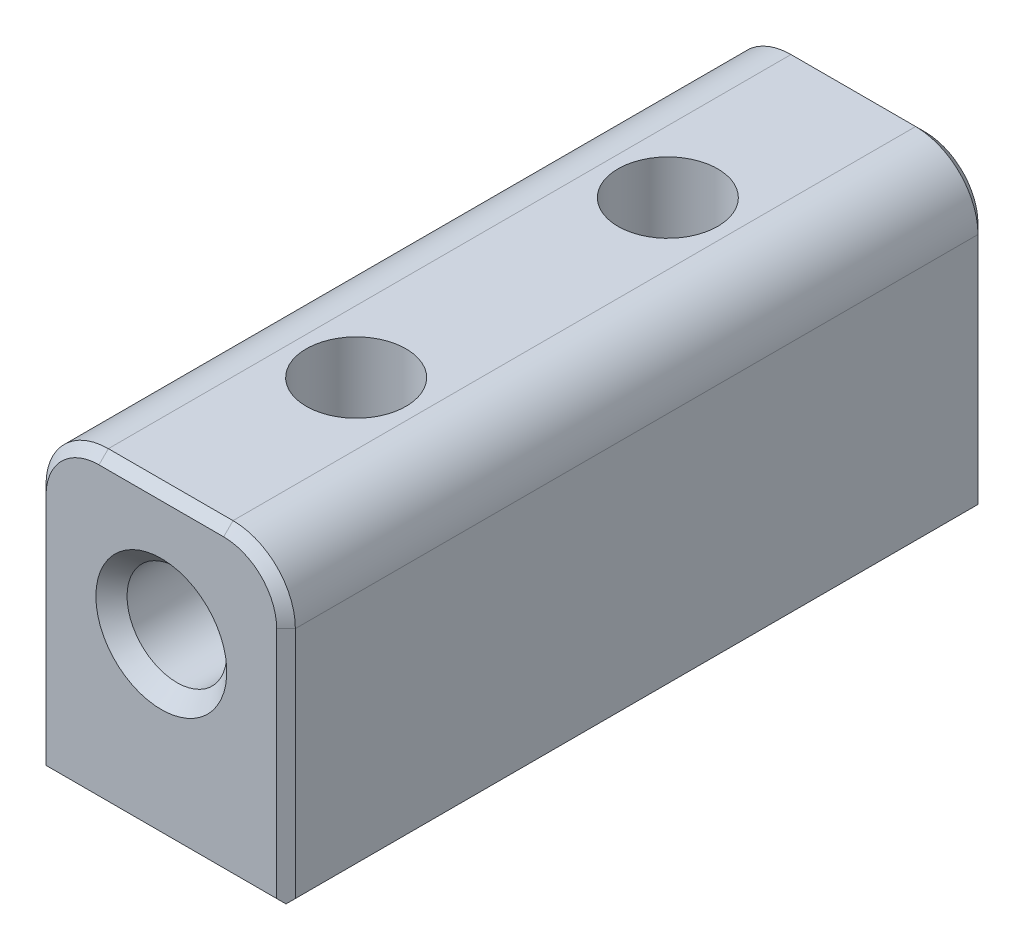
SolidWorks part; units mm, degrees
ref_plane "Front Plane" through (0, 0, 0) normal (0, 0, 1) x (1, 0, 0)
ref_plane "Top Plane" through (0, 0, 0) normal (0, 1, 0) x (1, 0, 0)
ref_plane "Right Plane" through (0, 0, 0) normal (1, 0, 0) x (0, 0, -1)
sketch "Sketch1" plane through (0, 0, 0) normal (0, 1, 0) x (1, 0, 0)
  line L0 (0, -6.35) -> (0, 6.35) construction
  line L1 (5.08, -14.2875) -> (-5.08, -14.2875)
  line L2 (5.08, -14.2875) -> (5.08, 14.2875)
  line L3 (5.08, 14.2875) -> (-5.08, 14.2875)
  line L4 (-5.08, -14.2875) -> (-5.08, 14.2875)
  line L5 (5.08, -14.2875) -> (-5.08, 14.2875) construction
  line L6 (5.08, 14.2875) -> (-5.08, -14.2875) construction
  circle A0 centre (0, 6.35) radius 2.032
  circle A1 centre (0, -6.35) radius 2.032
  point P0 (0, 0)
  point P9 (0, 0)
  dimension "D4" = 4.064
  dimension "D1" = 28.575
  dimension "D2" = 10.16
  dimension "D3" = 12.7
extrude "Boss-Extrude1" add sketch "Sketch1" along normal blind 12.7
sketch "Sketch2" plane through (0, 0, 14.2875) normal (0, 0, 1) x (1, 0, 0)
  line L0 (-5.08, 0) -> (5.08, 0) construction
  line L1 (-5.08, 12.7) -> (-5.08, 0) construction
  circle A0 centre (0, 7.62) radius 2.032
  dimension "D1" = 4.064
  dimension "D2" = 7.62
  dimension "D3" = 5.08
extrude "Cut-Extrude1" cut sketch "Sketch2" against normal blind 3.3274
sketch "Sketch4" plane through (0, 0, -14.2875) normal (0, 0, -1) x (-1, 0, 0)
  line L0 (-5.08, 0) -> (5.08, 0) construction
  line L1 (-5.08, 12.7) -> (-5.08, 0) construction
  circle A0 centre (0, 7.62) radius 2.032
  dimension "D1" = 4.064
  dimension "D2" = 7.62
  dimension "D3" = 5.08
extrude "Cut-Extrude2" cut sketch "Sketch4" against normal blind 3.3274
fillet "Fillet1" radius 2.54 2 edges at (5.08, 12.7, 0) (-5.08, 12.7, 0)
chamfer "Chamfer1" distance 0.635 angle 45 8 edges at (0, 0, 8.382) (0, 0, -4.318) (0, 0, 14.2875) (5.08, 0, 0) (0, 0, -14.2875) (-5.08, 0, 0) (-2.032, 7.62, -14.2875) (2.032, 7.62, 14.2875)
chamfer "Chamfer2" distance 0.381 angle 45 10 edges at (-5.08, 5.3975, -14.2875) (-4.3361, 11.9561, -14.2875) (0, 12.7, -14.2875) (4.3361, 11.9561, -14.2875) (5.08, 5.3975, -14.2875) (-5.08, 5.3975, 14.2875) (-4.3361, 11.9561, 14.2875) (0, 12.7, 14.2875) (4.3361, 11.9561, 14.2875) (5.08, 5.3975, 14.2875)
